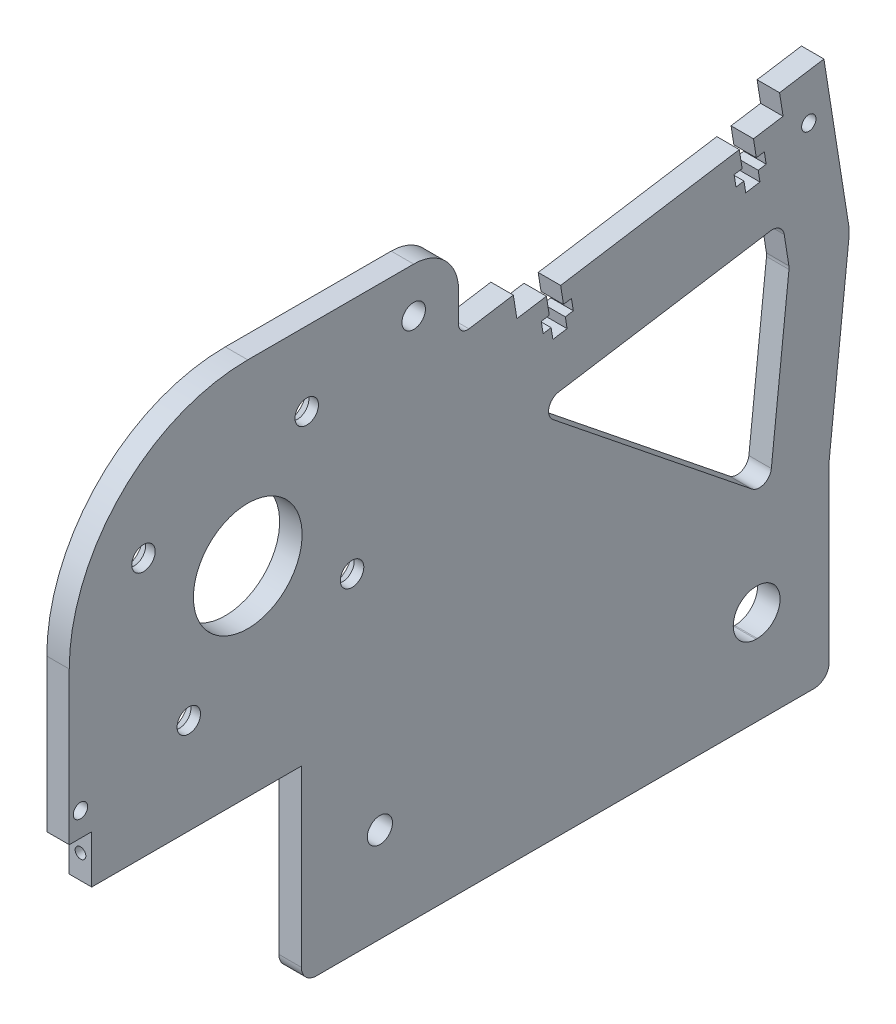
SolidWorks part; units mm, degrees
ref_plane "Front Plane" through (0, 0, 0) normal (0, 0, 1) x (1, 0, 0)
ref_plane "Top Plane" through (0, 0, 0) normal (0, 1, 0) x (1, 0, 0)
ref_plane "Right Plane" through (0, 0, 0) normal (1, 0, 0) x (0, 0, -1)
sketch "Sketch1" plane through (0, 0, 0) normal (1, 0, 0) x (0, 0, -1)
  line L0 (-28.1703, 0) -> (77.3828, 0)
  line L1 (80.5578, 3.175) -> (80.5578, 40.132)
  line L2 (-80.5578, 82.55) -> (-80.5578, 50.292)
  line L3 (4.1952, 102.6435) -> (13.6029, 104.1335)
  line L4 (-75.7953, 50.292) -> (-75.7953, 40.132)
  line L5 (-80.5578, 50.292) -> (-75.7953, 50.292)
  line L6 (65.3178, 20.066) -> (65.0638, 20.066) construction
  line L7 (-75.7953, 40.132) -> (-31.3453, 40.132)
  line L8 (1.9922, 110.875) -> (1.9922, 104.525)
  line L9 (-42.7078, 120.4) -> (-7.5328, 120.4)
  line L10 (-31.3453, 40.132) -> (-31.3453, 3.175)
  line L11 (-37.7935, 96.5728) -> (77.9184, 56.022) construction
  line L12 (-52.4128, 71.2982) -> (40.4331, -8.7847) construction
  line L13 (65.3178, 15.2273) -> (65.0638, 15.2273)
  line L14 (65.3178, 24.9047) -> (65.0638, 24.9047)
  line L15 (4.1952, 102.6435) -> (101.0919, 102.6435) construction
  line L16 (13.6029, 104.1335) -> (14.348, 99.4297)
  line L17 (14.348, 99.4297) -> (20.6198, 100.423)
  line L18 (70.7944, 108.3699) -> (70.0493, 113.0738)
  line L19 (70.0493, 113.0738) -> (79.4571, 114.5638)
  line L20 (79.4571, 114.5638) -> (84.7184, 81.3449)
  line L21 (84.7717, 79.1961) -> (80.5578, 40.132)
  line L22 (20.6198, 100.423) -> (21.2208, 96.6286)
  line L23 (21.2208, 96.6286) -> (19.5274, 96.3604)
  line L24 (19.5274, 96.3604) -> (19.9198, 93.883)
  line L25 (19.9198, 93.883) -> (21.6131, 94.1512)
  line L26 (26.317, 94.8962) -> (25.9246, 97.3736)
  line L27 (25.9246, 97.3736) -> (24.2312, 97.1054)
  line L28 (24.2312, 97.1054) -> (23.6303, 100.8998)
  line L29 (23.6303, 100.8998) -> (61.5121, 106.8997)
  line L30 (64.5225, 107.3765) -> (70.7944, 108.3699)
  line L31 (71.0359, 86.549) -> (72.0272, 80.29)
  line L38 (21.6131, 94.1512) -> (21.9857, 91.7993)
  line L39 (21.9857, 91.7993) -> (24.9961, 92.2761)
  line L40 (24.9961, 92.2761) -> (24.6236, 94.628)
  line L41 (24.6236, 94.628) -> (26.317, 94.8962)
  line L46 (61.5121, 106.8997) -> (62.113, 103.1053)
  line L47 (68.1298, 88.6604) -> (23.2189, 81.5472)
  line L48 (22.0267, 77.0573) -> (64.1879, 43.2308)
  line L49 (68.3027, 44.9396) -> (72.0438, 79.6202)
  line L50 (62.113, 103.1053) -> (60.4196, 102.8371)
  line L51 (60.4196, 102.8371) -> (60.812, 100.3597)
  line L52 (60.812, 100.3597) -> (62.5054, 100.6279)
  line L53 (67.2093, 101.3729) -> (66.8169, 103.8503)
  line L54 (66.8169, 103.8503) -> (65.1235, 103.5821)
  line L55 (65.1235, 103.5821) -> (64.5225, 107.3765)
  line L56 (62.5054, 100.6279) -> (62.8779, 98.276)
  line L57 (62.8779, 98.276) -> (65.8884, 98.7528)
  line L58 (65.8884, 98.7528) -> (65.5159, 101.1047)
  line L59 (65.5159, 101.1047) -> (67.2093, 101.3729)
  arc A0 (65.3178, 15.2273) -> (65.3178, 24.9047) centre (65.3178, 20.066) ccw
  circle A1 centre (-42.7078, 82.55) radius 31.5 construction
  circle A2 centre (65.3178, 20.066) radius 78.105 construction
  circle A3 centre (65.3178, 20.066) radius 38.1 construction
  circle A4 centre (-42.7078, 82.55) radius 14.859 construction
  arc A5 (-42.7078, 120.4) -> (-80.5578, 82.55) centre (-42.7078, 82.55) ccw
  arc A6 (-28.1703, 0) -> (-31.3453, 3.175) centre (-28.1703, 3.175) cw
  arc A7 (77.3828, 0) -> (80.5578, 3.175) centre (77.3828, 3.175) ccw
  circle A9 centre (-7.5328, 110.875) radius 6.35 construction
  circle A10 centre (-55.209, 60.4394) radius 2.4892
  circle A11 centre (-14.6922, 20.066) radius 2.667
  circle A12 centre (-20.5972, 70.0488) radius 2.4892
  circle A13 centre (-64.8184, 95.0512) radius 2.4892
  circle A14 centre (-30.2065, 104.6606) radius 2.4892
  circle A15 centre (-78.1765, 55.372) radius 1.524
  circle A16 centre (-42.7078, 82.55) radius 11.5228
  arc A17 (65.0638, 24.9047) -> (65.0638, 15.2273) centre (65.0638, 20.066) ccw
  arc A18 (-7.5328, 120.4) -> (1.9922, 110.875) centre (-7.5328, 110.875) cw
  circle A19 centre (-7.5328, 110.875) radius 2.4892
  arc A20 (4.1952, 102.6435) -> (1.9922, 104.525) centre (3.8972, 104.525) cw
  arc A21 (84.7184, 81.3449) -> (84.7717, 79.1961) centre (76.6695, 80.0701) cw
  circle A22 centre (76.2432, 104.411) radius 1.524
  arc A23 (72.0438, 79.6202) -> (72.0272, 80.29) centre (69.5185, 79.8927) ccw
  arc A24 (64.1879, 43.2308) -> (68.3027, 44.9396) centre (65.7774, 45.212) ccw
  arc A25 (23.2189, 81.5472) -> (22.0267, 77.0573) centre (23.6162, 79.0385) ccw
  arc A26 (68.1298, 88.6604) -> (71.0359, 86.549) centre (68.5271, 86.1517) cw
  point P39 (65.1908, 20.066)
  dimension "D4" = 9.6774
  dimension "D7" = 29.718
  dimension "D8" = 63
  dimension "D9" = 6.35
  dimension "D12" = 3.175
  dimension "D13" = 4.7625
  dimension "D14" = 76.2
  dimension "D15" = 156.21
  dimension "D18" = 5.334
  dimension "D19" = 9.525
  dimension "D20" = 9.525
  dimension "D23" = 3.048
  dimension "D27" = 73.025
  dimension "D28" = 12.7
  dimension "D29" = 4.9784
  dimension "D31" = 1.905
  dimension "D33" = 3.048
  dimension "D42" = 2.54
  dimension "D43" = 2.54
  dimension "D44" = 86.36
  dimension "D48" = 3.048
  dimension "D49" = 9.525
  dimension "D2" = 40.132
  dimension "D3" = 20.066
  dimension "D5" = 15.24
  dimension "D6" = 44.45
  dimension "D10" = 161.1156
  dimension "D11" = 95.25
  dimension "D17" = 9
  dimension "D21" = 4.7625
  dimension "D22" = 10.16
  dimension "D24" = 5.08
  dimension "D25" = 2.3813
  dimension "D26" = 0.254
  dimension "D16" = 76.2
  dimension "D30" = 9.525
  dimension "D34" = 19.05
  dimension "D35" = 8.7312
  dimension "D36" = 2.5083
  dimension "D37" = 6.477
  dimension "D38" = 6.35
  dimension "D40" = 12.7
  dimension "D45" = 6.35
  dimension "D46" = 6.35
  dimension "D47" = 4.7625
  dimension "D50" = 5.08
  dimension "D39" = 2
extrude "Boss-Extrude1" add sketch "Sketch1" along normal blind 4.7625
sketch "Sketch2" plane through (0, 0, 75.7953) normal (0, 0, 1) x (1, 0, 0)
  line L0 (4.7625, 50.292) -> (4.7625, 40.132) construction
  line L1 (4.7625, 40.132) -> (0, 40.132) construction
  circle A0 centre (2.3813, 45.212) radius 1.1303
  point P4 (4.7625, 45.212)
  point P7 (2.3813, 40.132)
  dimension "D1" = 2.2606
extrude "Cut-Extrude1" cut sketch "Sketch2" against normal blind 6.35
chamfer "Chamfer1" distance 2.7305 angle 41 4 edges at (0, 95.0512, 62.3292) (0, 60.4394, 52.7198) (0, 70.0488, 18.108) (0, 104.6606, 27.7173) first distance on face at (4.7625, 95.0512, 62.3292) first distance on face at (4.7625, 60.4394, 52.7198) first distance on face at (4.7625, 70.0488, 18.108) first distance on face at (4.7625, 104.6606, 27.7173)
